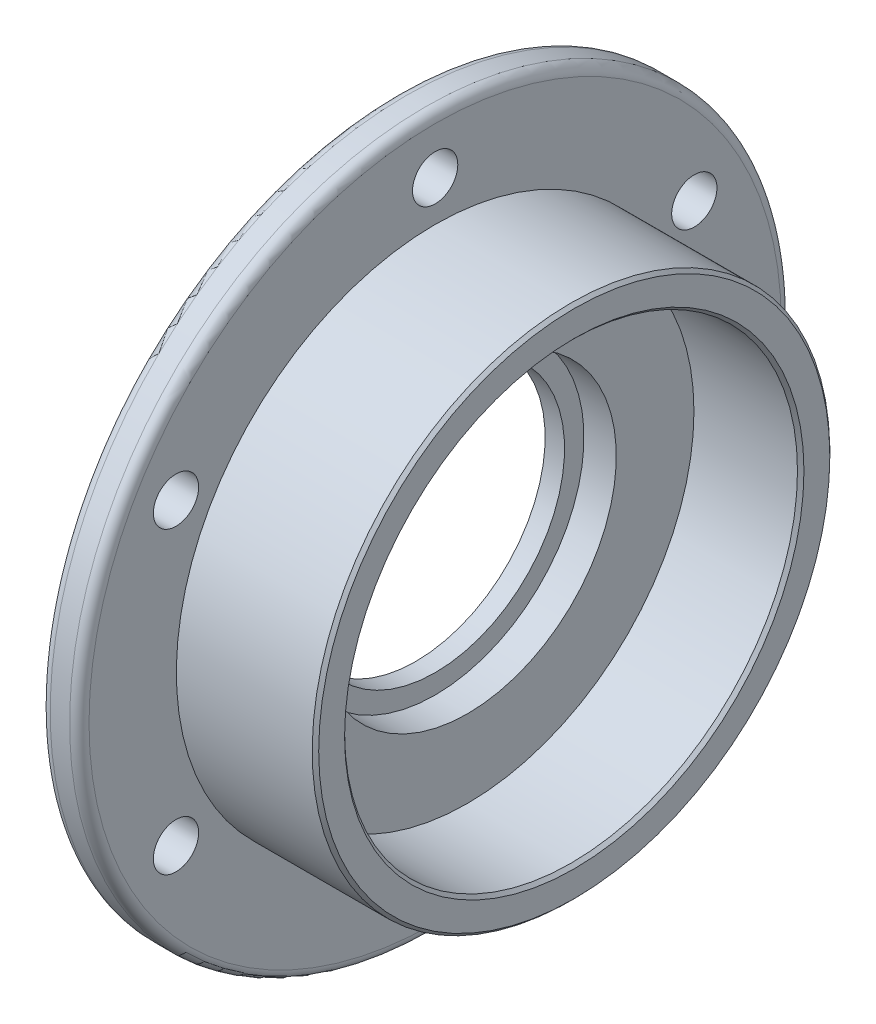
SolidWorks part; units mm, degrees
material "Cast Alloy Steel"
ref_plane "Front Plane" through (0, 0, 0) normal (0, 0, 1) x (1, 0, 0)
ref_plane "Top Plane" through (0, 0, 0) normal (0, 1, 0) x (1, 0, 0)
ref_plane "Right Plane" through (0, 0, 0) normal (1, 0, 0) x (0, 0, -1)
sketch "Sketch1" plane through (0, 0, 0) normal (0, 0, 1) x (1, 0, 0)
  line L0 (0, 0) -> (0, 75)
  line L1 (0, 75) -> (-6, 75)
  line L2 (-6, 75) -> (-6, 110)
  line L3 (-6, 110) -> (6, 110)
  line L4 (6, 110) -> (6, 80)
  line L5 (6, 80) -> (49, 80)
  line L6 (49, 80) -> (49, 70)
  line L7 (49, 70) -> (6, 70)
  line L8 (6, 70) -> (6, 0)
  line L9 (6, 0) -> (0, 0) construction
  line L10 (0, 0) -> (6, 0)
  dimension "D1" = 160
  dimension "D2" = 140
  dimension "D3" = 220
  dimension "D4" = 150
  dimension "L1" = 12
  dimension "L2" = 43
  dimension "L3" = 6
revolve "Revolve1" add sketch "Sketch1" angle 360 about L9
sketch "Sketch2" plane through (-6, 0, 0) normal (-1, 0, 0) x (0, 0, 1)
  circle A0 centre (0, 0) radius 92.5 construction
  circle A1 centre (0, 92.5) radius 7
  dimension "D1" = 14
  dimension "D5" = 185
extrude "Cut-Extrude1" cut sketch "Sketch2" against normal through all
pattern_circular "CirPattern1" count 6 over 360 about axis through (6, 0, 0) along (1, 0, 0) of "Cut-Extrude1" reverse direction yes
fillet "Fillet1" radius 3 4 edges at (-6, 75, 0) (0, 75, 0) (6, 110, 0) (-6, 110, 0)
chamfer "Chamfer1" distance 1 angle 45 2 edges at (49, 70, 0) (49, 80, 0)
sketch "Sketch3" plane through (0, 0, 0) normal (-1, 0, 0) x (0, 0, 1)
  circle A0 centre (0, 0) radius 40
  dimension "D1" = 80
extrude "Cut-Extrude2" cut sketch "Sketch3" against normal through all
sketch "Sketch4" plane through (6, 0, 0) normal (1, 0, 0) x (0, 0, -1)
  circle A2 centre (0, 0) radius 46
  circle A3 centre (0, 0) radius 46
  circle A4 centre (0, 0) radius 70
  circle A5 centre (0, 0) radius 70
  dimension "D1" = 24
  dimension "D2" = 0
extrude "Boss-Extrude1" add sketch "Sketch4" along normal blind 10
